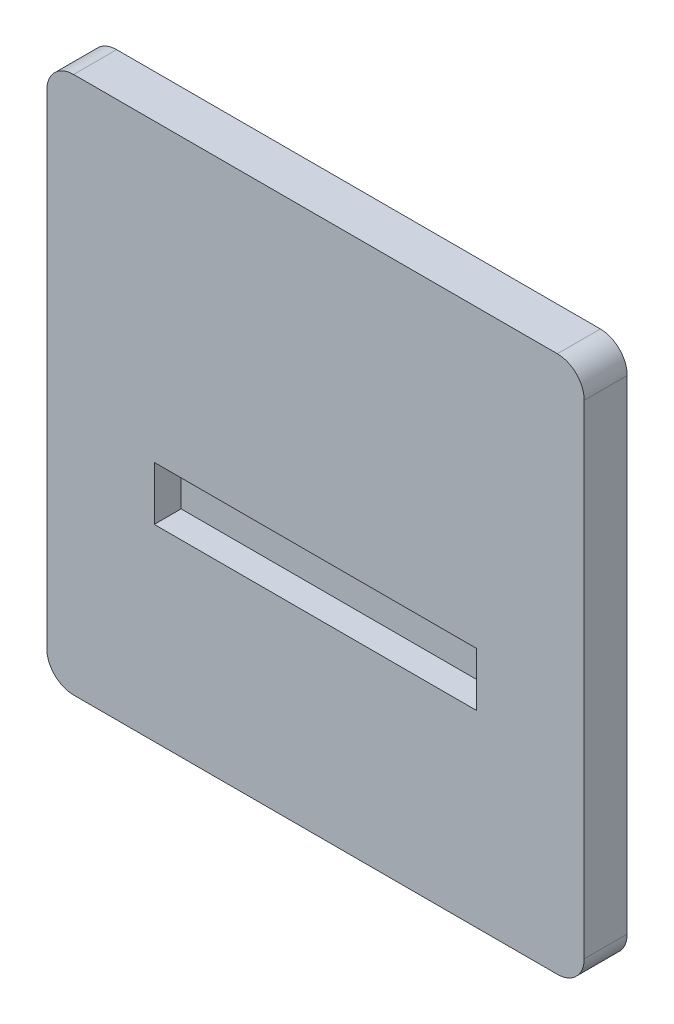
SolidWorks part; units mm, degrees
ref_plane "Front" through (0, 0, 0) normal (0, 0, 1) x (1, 0, 0)
ref_plane "Top" through (0, 0, 0) normal (0, 1, 0) x (1, 0, 0)
ref_plane "Right" through (0, 0, 0) normal (1, 0, 0) x (0, 0, -1)
sketch "Esquisse1" plane through (0, 0, 0) normal (0, 0, 1) x (1, 0, 0)
  line L1 (0, 0) -> (100, 0)
  line L2 (0, 0) -> (0, 100)
  line L3 (0, 100) -> (100, 100)
  line L4 (100, 0) -> (100, 100)
  dimension "D1" = 100
  dimension "D2" = 100
extrude "Boss.-Extru.1" add sketch "Esquisse1" along normal blind 8
sketch "Esquisse2" plane through (0, 0, 8) normal (0, 0, 1) x (1, 0, 0)
  line L1 (20, 45) -> (80, 45)
  line L2 (20, 45) -> (20, 35)
  line L3 (20, 35) -> (80, 35)
  line L4 (80, 45) -> (80, 35)
  line L6 (100, 100) -> (0, 100) construction
  line L7 (50, 35) -> (50, 0) construction
  line L8 (0, 0) -> (100, 0) construction
  dimension "D1" = 10
  dimension "D2" = 55
  dimension "D3" = 60
extrude "Enlèv. mat.-Extru.1" cut sketch "Esquisse2" against normal blind 5
fillet "Congé1" radius 5 4 edges at (100, 0, 4) (0, 0, 4) (0, 100, 4) (100, 100, 4)
